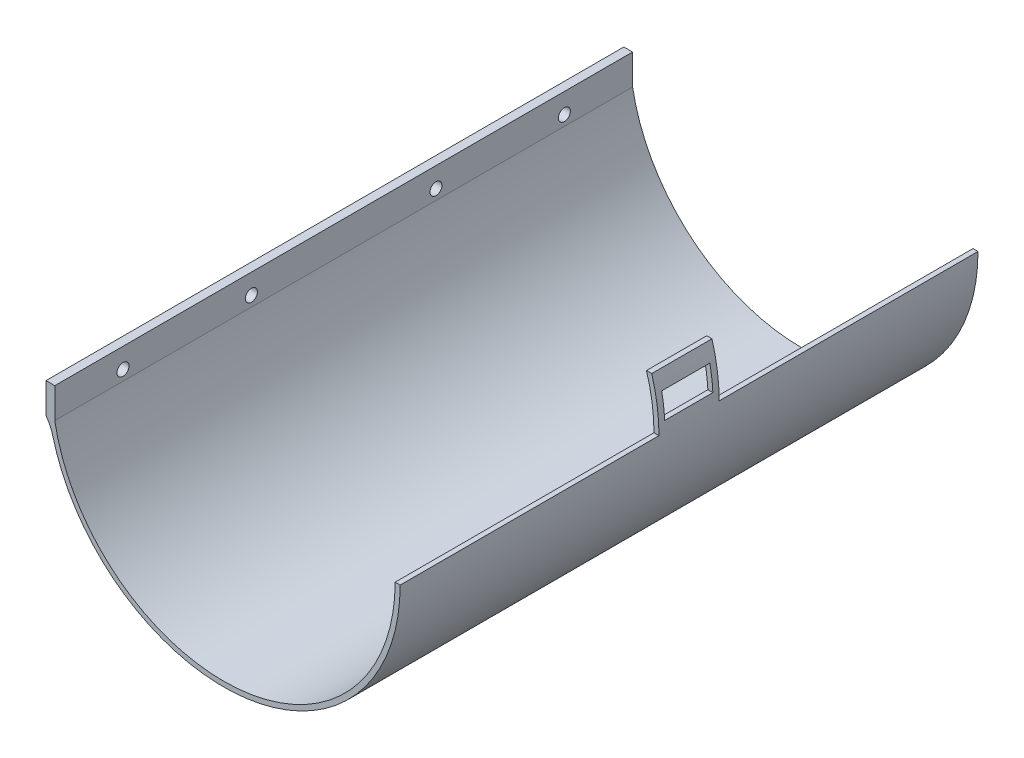
SolidWorks part; units mm, degrees
ref_plane "Front Plane" through (0, 0, 0) normal (0, 0, 1) x (1, 0, 0)
ref_plane "Top Plane" through (0, 0, 0) normal (0, 1, 0) x (1, 0, 0)
ref_plane "Right Plane" through (0, 0, 0) normal (1, 0, 0) x (0, 0, -1)
sketch "Sketch1" plane through (0, 0, 0) normal (0, 0, 1) x (1, 0, 0)
  line L0 (-44, 0) -> (-42.75, 0)
  line L1 (42.75, 0) -> (44, 0)
  arc A0 (-44, 0) -> (44, 0) centre (0, 0) ccw
  arc A1 (-42.75, 0) -> (42.75, 0) centre (0, 0) ccw
  dimension "D1" = 88
  dimension "D2" = 85.5
extrude "Boss-Extrude1" add sketch "Sketch1" along normal blind 144
sketch "Sketch2" plane through (0, 0, 0) normal (1, 0, 0) x (0, 0, -1)
  line L0 (-144, 0) -> (-144, -44) construction
  line L1 (0, -44) -> (0, 0) construction
  line L2 (-144, 0) -> (0, 0) construction
  circle A0 centre (-127, -5) radius 1.5
  circle A1 centre (-95, -5) radius 1.5
  circle A2 centre (-49, -5) radius 1.5
  circle A3 centre (-17, -5) radius 1.5
  dimension "D1" = 3
  dimension "D2" = 3
  dimension "D3" = 3
  dimension "D4" = 3
  dimension "D5" = 32
  dimension "D6" = 32
  dimension "D7" = 17
  dimension "D8" = 17
  dimension "D9" = 46
  dimension "D10" = 5
extrude "Cut-Extrude1" cut sketch "Sketch2" against normal up to surface (43.715 mm away) up to face at (0, -22, 72)
ref_plane "Plane1" through (0, 0, 72) normal (0, 0, -1) x (-1, 0, 0)
sketch "Sketch4" plane through (0, 0, 72) normal (0, 0, -1) x (-1, 0, 0)
  line L0 (-42.1884, 12.4954) -> (-40.8831, 12.4954)
  line L1 (-44, 0) -> (-42.75, 0)
  arc A0 (-40.8831, 12.4954) -> (-42.75, 0) centre (0, 0) ccw
  arc A1 (-42.1884, 12.4954) -> (-44, 0) centre (0, 0) ccw
  point P1 (-40.153, 13.928)
  point P3 (-40.9742, 11.2857)
  point P8 (-40.644, 12.4223)
  dimension "D1" = 88
  dimension "D2" = 85.5
extrude "Boss-Extrude2" add sketch "Sketch4" along normal blind 7.5 and the other way blind 7.5
sketch "Sketch5" plane through (0, 0, 144) normal (0, 0, 1) x (1, 0, 0)
  line L5 (-44, 0) -> (-44, -7.5543)
  line L6 (-44, -7.5543) -> (-42.7628, -7.5543)
  line L7 (-42.7628, -7.5543) -> (-42.7628, 0)
  line L8 (-42.75, 0) -> (-44, 0) construction
  line L9 (-42.7628, 0) -> (-44, 0)
extrude "Cut-Extrude2" cut sketch "Sketch5" against normal up to surface (144 mm away) up to face at (0, -21.6875, 0)
sketch "Sketch6" plane through (-42.7628, 0, 0) normal (-1, 0, 0) x (0, 0, 1)
  line L1 (0, -7.5543) -> (144, -7.5543)
  line L2 (0, -7.5543) -> (0, 0)
  line L3 (0, 0) -> (144, 0)
  line L4 (144, -7.5543) -> (144, 0)
  circle A0 centre (17, -5) radius 1.5
  circle A1 centre (49, -5) radius 1.5
  circle A2 centre (95, -5) radius 1.5
  circle A3 centre (127, -5) radius 1.5
  circle M5 centre (49, -5) radius 1.5
  circle M6 centre (127, -5) radius 1.5
  line M7 (0, 0) -> (0, -7.5543)
  line M8 (0, -7.5543) -> (144, -7.5543)
  line M9 (144, -7.5543) -> (144, 0)
  line M10 (144, 0) -> (0, 0)
  circle M11 centre (95, -5) radius 1.5
  circle M12 centre (17, -5) radius 1.5
extrude "Boss-Extrude3" add sketch "Sketch6" along normal blind 0.5 contours M10 M7 M8 M9 M6 M11 M12 M5 region at (-42.7628, -3.7445, 72)
sketch "Sketch7" plane through (0, 0, 144) normal (0, 0, 1) x (1, 0, 0)
  line L0 (3.1936, -47.2716) -> (4.2473, -46.1824)
  line L2 (2.6526, -44.3202) -> (7.0646, -42.9225)
  line L3 (2.6526, -44.3202) -> (-0.0812, -45.0066)
  line L4 (-2.6526, -44.3202) -> (-7.0646, -42.9225)
  arc A1 (-0.0812, -45.0066) -> (3.1936, -47.2716) centre (-0.0812, -48.5066) ccw
  arc A2 (-2.6526, -44.3202) -> (4.2473, -46.1824) centre (-0.0812, -48.5066) ccw
  arc A3 (-7.0646, -42.9225) -> (7.0646, -42.9225) centre (0, 0) ccw
  dimension "D1" = 43.5
  dimension "D2" = 7
extrude "Boss-Extrude4" add sketch "Sketch7" against normal blind 77
fillet "Fillet3" radius 0.5 1 edges at (4.2473, -46.1824, 105.5)
sketch "Sketch9" plane through (0, 0, 0) normal (1, 0, 0) x (0, 0, -1)
  line L0 (-79.5, 12.4954) -> (-79.5, 0) construction
  line L1 (-78, 8.4954) -> (-66, 8.4954)
  line L2 (-78, 8.4954) -> (-78, 2.4954)
  line L3 (-78, 2.4954) -> (-66, 2.4954)
  line L4 (-66, 8.4954) -> (-66, 2.4954)
  line L5 (-79.5, 12.4954) -> (-64.5, 12.4954) construction
  dimension "D1" = 12
  dimension "D2" = 6
  dimension "D3" = 1.5
  dimension "D4" = 4
extrude "Cut-Extrude4" cut sketch "Sketch9" along normal up to surface (43.1721 mm away) up to face at (15.0324, -18.3013, 83.1667)
sketch "Sketch11" plane through (0, 0, 144) normal (0, 0, 1) x (1, 0, 0)
  line L1 (6.0382, -53.7585) -> (4.3409, -43.7853)
  line L2 (6.0382, -53.7585) -> (2.0015, -51.3196)
  line L3 (-6.6638, -46.7537) -> (-4.3409, -43.7853)
  line L4 (2.6526, -44.3202) -> (4.3409, -43.7853) construction
  arc A1 (-6.6638, -46.7537) -> (6.0382, -53.7585) centre (2.0015, -46.0596) ccw
  arc A2 (-4.3409, -43.7853) -> (4.3409, -43.7853) centre (0, 0) ccw
  arc A3 (-0.0812, -45.0066) -> (3.1936, -47.2716) centre (-0.0812, -48.5066) ccw construction
  arc A4 (4.3409, -43.7853) -> (44, 0) centre (0, 0) ccw construction
  point P1 (6.0727, -53.9615)
  point P3 (2.0015, -51.3196)
  point P9 (4.3409, -43.7853)
  point P10 (-4.3409, -43.7853)
  point P12 (4.3409, -43.7853)
  dimension "D1" = 44
extrude "Cut-Extrude5" cut sketch "Sketch11" against normal blind 67 contours A1 L3 A2 L1
sketch "Sketch12" plane through (0, 0, 0) normal (0, 0, -1) x (-1, 0, 0)
  line L2 (42.75, 0) -> (42.75, -7.5543)
  line L6 (42.75, -7.5543) -> (41.523, -7.5543)
  line L7 (41.523, -7.5543) -> (42.75, 0)
extrude "Cut-Extrude6" cut sketch "Sketch12" against normal up to surface (144 mm away) up to face at (-13.7346, -16.3196, 144)
sketch "Sketch14" plane through (-43.2628, 0, 0) normal (-1, 0, 0) x (0, 0, 1)
  line L0 (0, -7.5543) -> (144, -7.5543) construction
  line L1 (0, 0) -> (144, 0)
  line L2 (0, 0) -> (0, -7.5543)
  line L3 (0, -7.5543) -> (144, -7.5543)
  line L4 (144, 0) -> (144, -7.5543)
  line L5 (144, -7.5543) -> (144, 0) construction
  circle A0 centre (17, -5) radius 1.5
  circle A1 centre (49, -5) radius 1.5
  circle A2 centre (95, -5) radius 1.5
  circle A3 centre (127, -5) radius 1.5
  point P18 (143.8212, -7.5543)
  point P21 (144, -7.5543)
extrude "Boss-Extrude5" add sketch "Sketch14" along normal blind 1 and the other way blind 1.5
sketch "Sketch17" plane through (0, -7.5543, 0) normal (0, -1, 0) x (1, 0, 0)
  line L1 (-42.0773, 144) -> (-41.7628, 144)
  line L2 (-42.0773, 144) -> (-42.0773, 0)
  line L3 (-42.0773, 0) -> (-41.7628, 0)
  line L4 (-41.7628, 144) -> (-41.7628, 0)
extrude "Cut-Extrude8" cut sketch "Sketch17" against normal up to surface (7.5543 mm away) up to face at (-43.0128, 0, 72)
fillet "Fillet4" radius 10 1 edges at (-43.3467, -7.5543, 72)
